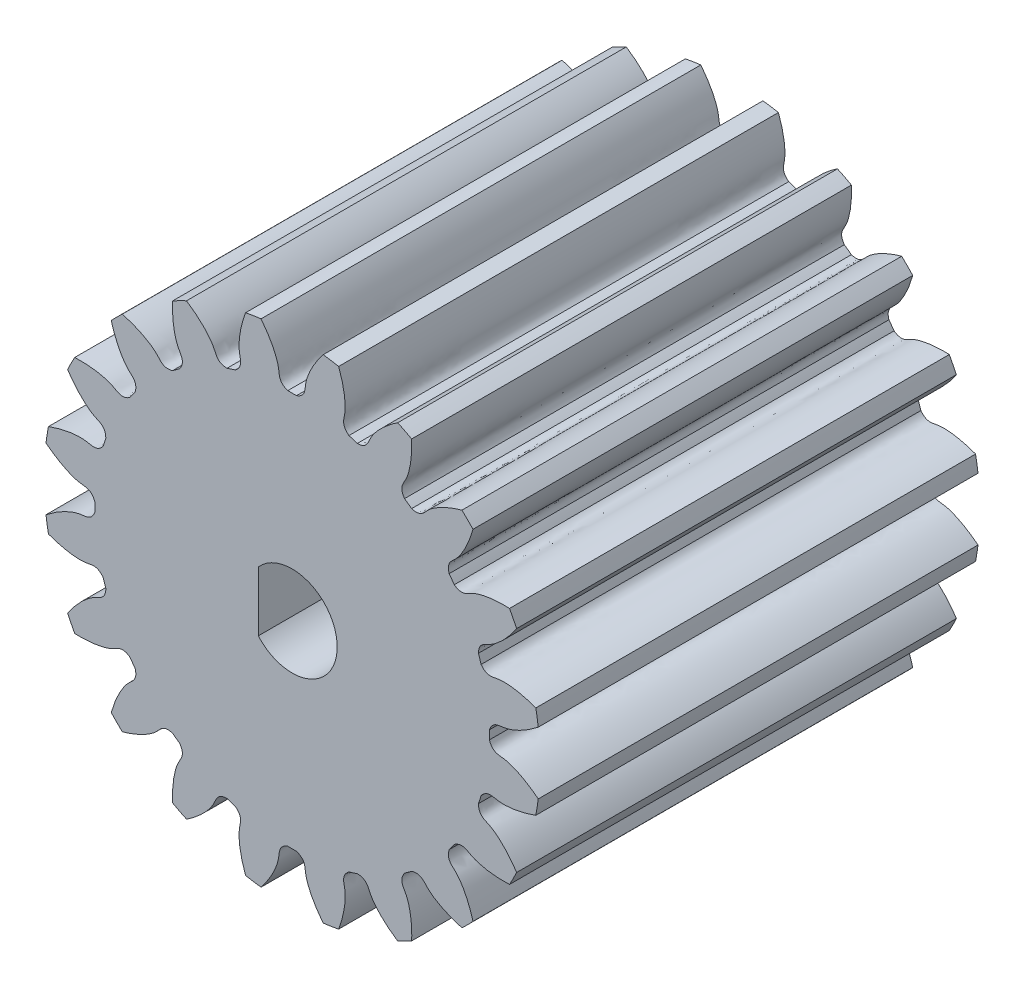
SolidWorks part; units mm, degrees
ref_plane "前视基准面" through (0, 0, 0) normal (0, 0, 1) x (1, 0, 0)
ref_plane "上视基准面" through (0, 0, 0) normal (0, 1, 0) x (1, 0, 0)
ref_plane "右视基准面" through (0, 0, 0) normal (1, 0, 0) x (0, 0, -1)
other "Configuration Table"
sketch "草图1" plane through (0, 0, 0) normal (0, 0, 1) x (1, 0, 0)
  circle A0 centre (0, 0) radius 11
extrude "凸台-拉伸1" add sketch "草图1" along normal blind 19.5
ref_axis "基准轴1" through (0, 0, -1.5) along (0, 0, 1)
sketch "草图2" plane through (0, 0, 0) normal (0, 0, 1) x (1, 0, 0)
  line L0 (0, 0) -> (0, 11) construction
  circle A0 centre (0, 0) radius 11 construction
  arc A1 (0.1933, 8.7479) -> (-0.1933, 8.7479) centre (0, 0) ccw
  arc A2 (3.1812, 12.4983) -> (-3.1812, 12.4983) centre (0, 0) ccw
  spline S0 degree 3 poles (0.1933, 8.7479) (0.6112, 8.8935) (0.5571, 9.1871) (0.6129, 9.47) (0.6189, 9.4976) (0.6263, 9.5286) (0.6353, 9.5632) (0.646, 9.6012) (0.6585, 9.6426) (0.673, 9.6873) (0.6897, 9.7352) (0.7086, 9.7863) (0.7299, 9.8406) (0.7537, 9.8978) (0.7801, 9.958) (0.8094, 10.0211) (0.8415, 10.087) (0.8767, 10.1556) (0.915, 10.2267) (0.9566, 10.3004) (1.0015, 10.3764) (1.05, 10.4548) (1.102, 10.5352) (1.1578, 10.6178) (1.2173, 10.7023) (1.2808, 10.7886) (1.3482, 10.8766) (1.4198, 10.9662) (1.4955, 11.0572) (1.5755, 11.1496) (1.6598, 11.2431) (1.7486, 11.3376) (1.8418, 11.4331) (1.9397, 11.5293) (2.0421, 11.6261) (2.1493, 11.7233) (2.2612, 11.8209) (2.378, 11.9186) (2.4996, 12.0163) (2.6261, 12.1139) (2.7575, 12.2112) (2.9415, 12.3416) (3.0839, 12.4363) (3.1812, 12.4983) knots 0 0 0 0 0.165916 0.170906 0.176664 0.183189 0.190482 0.198542 0.207371 0.216967 0.22733 0.238462 0.250361 0.263027 0.276462 0.290664 0.305634 0.321371 0.337876 0.355149 0.37319 0.391998 0.411574 0.431917 0.453028 0.474907 0.497554 0.520968 0.54515 0.570099 0.595817 0.622302 0.649554 0.677575 0.706363 0.735918 0.766242 0.797333 0.829191 0.861818 0.895212 0.929373 1 1 1 1
  spline S1 degree 3 poles (-0.1933, 8.7479) (-0.6112, 8.8935) (-0.5571, 9.1871) (-0.6129, 9.47) (-0.6189, 9.4976) (-0.6263, 9.5286) (-0.6353, 9.5632) (-0.646, 9.6012) (-0.6585, 9.6426) (-0.673, 9.6873) (-0.6897, 9.7352) (-0.7086, 9.7863) (-0.7299, 9.8406) (-0.7537, 9.8978) (-0.7801, 9.958) (-0.8094, 10.0211) (-0.8415, 10.087) (-0.8767, 10.1556) (-0.915, 10.2267) (-0.9566, 10.3004) (-1.0015, 10.3764) (-1.05, 10.4548) (-1.102, 10.5352) (-1.1578, 10.6178) (-1.2173, 10.7023) (-1.2808, 10.7886) (-1.3482, 10.8766) (-1.4198, 10.9662) (-1.4955, 11.0572) (-1.5755, 11.1496) (-1.6598, 11.2431) (-1.7486, 11.3376) (-1.8418, 11.4331) (-1.9397, 11.5293) (-2.0421, 11.6261) (-2.1493, 11.7233) (-2.2612, 11.8209) (-2.378, 11.9186) (-2.4996, 12.0163) (-2.6261, 12.1139) (-2.7575, 12.2112) (-2.9415, 12.3416) (-3.0839, 12.4363) (-3.1812, 12.4983) knots 0 0 0 0 0.165916 0.170906 0.176664 0.183189 0.190482 0.198542 0.207371 0.216967 0.22733 0.238462 0.250361 0.263027 0.276462 0.290664 0.305634 0.321371 0.337876 0.355149 0.37319 0.391998 0.411574 0.431917 0.453028 0.474907 0.497554 0.520968 0.54515 0.570099 0.595817 0.622302 0.649554 0.677575 0.706363 0.735918 0.766242 0.797333 0.829191 0.861818 0.895212 0.929373 1 1 1 1
extrude "切除-拉伸1" cut sketch "草图2" along normal through all
pattern_circular "阵列(圆周)1" count 20 every 18 about axis through (0, 0, -1.5) along (0, 0, 1) of "切除-拉伸1"
sketch "草图3" plane through (0, 0, 0) normal (0, 0, 1) x (1, 0, 0)
  circle A0 centre (0, 0) radius 10 construction
  dimension "Dn" = 20
sketch "草图4" plane through (0, 0, 19.5) normal (0, 0, 1) x (1, 0, 0)
  line L0 (-1.5, 1.3229) -> (-1.5, -1.3229)
  arc A0 (-1.5, -1.3229) -> (-1.5, 1.3229) centre (0, 0) ccw
  dimension "D1" = 4
  dimension "D2" = 1.5
extrude "切除-拉伸2" cut sketch "草图4" against normal blind 10
